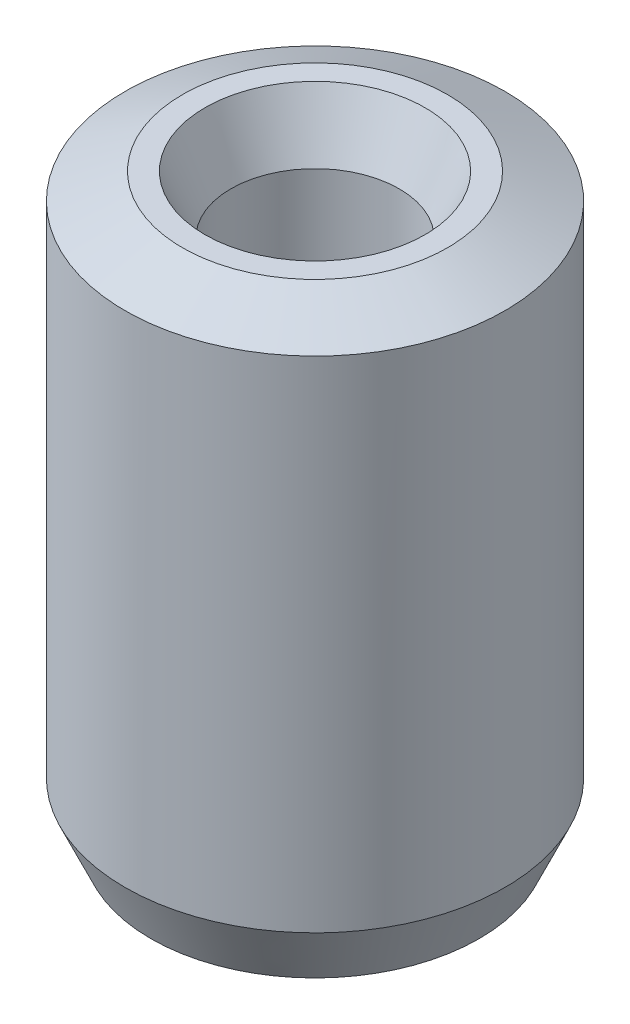
SolidWorks part; units mm, degrees
ref_plane "Front Plane" through (0, 0, 0) normal (0, 0, 1) x (1, 0, 0)
ref_plane "Top Plane" through (0, 0, 0) normal (0, 1, 0) x (1, 0, 0)
ref_plane "Right Plane" through (0, 0, 0) normal (1, 0, 0) x (0, 0, -1)
sketch "Sketch1" plane through (0, 0, 0) normal (0, 1, 0) x (1, 0, 0)
  circle A0 centre (0, 0) radius 27.5
  dimension "SLEEVE_OD" = 55
extrude "Boss-Extrude1" add sketch "Sketch1" along normal blind 84.3538
sketch "Sketch2" plane through (0, 0, 0) normal (0, 1, 0) x (1, 0, 0)
  circle A0 centre (0, 0) radius 12.1893
  dimension "BORE_D" = 24.3786
extrude "Cut-Extrude1" cut sketch "Sketch2" along normal through all
chamfer "Chamfer1" distance 3.7425 angle 65.728 4 edges at (0, 84.3538, 12.1893) (0, 0, 12.1893) (0, 0, 27.5) (0, 84.3538, 27.5) first distance on face at (0, 84.3538, 12.1893) first distance on face at (0, 0, 12.1893) first distance on face at (0, 84.3538, 27.5)
